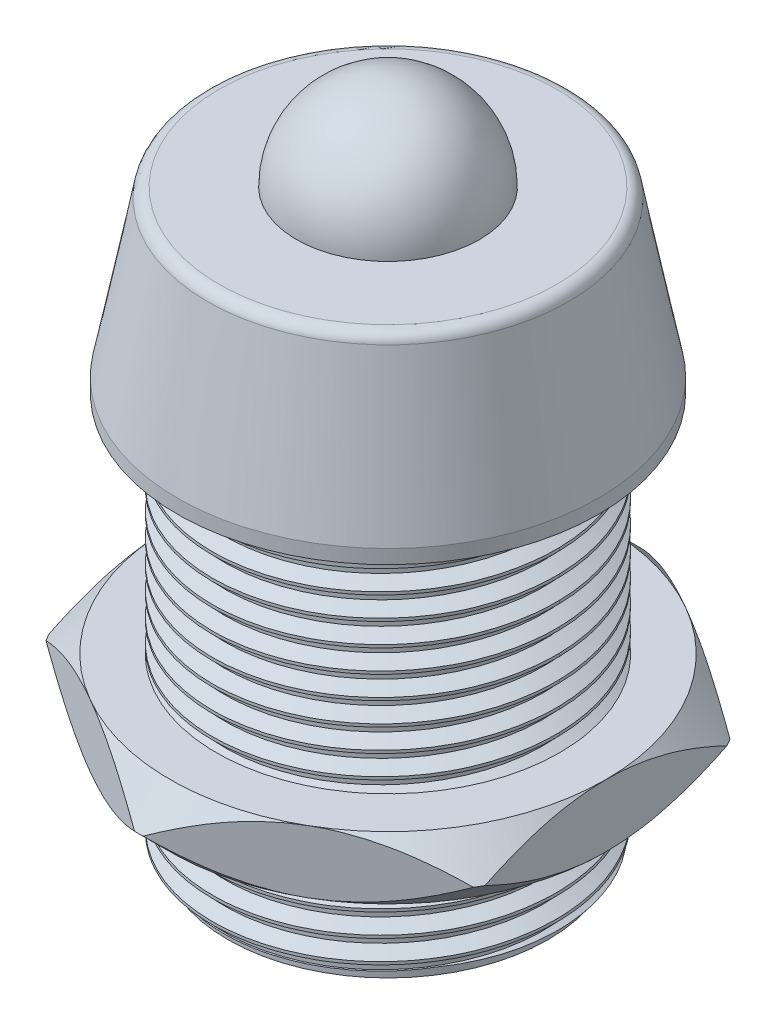
SolidWorks part; units mm, degrees
material "Stainless Steel (ferritic)"
ref_plane "Front Plane" through (0, 0, 0) normal (0, 0, 1) x (1, 0, 0)
ref_plane "Top Plane" through (0, 0, 0) normal (0, 1, 0) x (1, 0, 0)
ref_plane "Right Plane" through (0, 0, 0) normal (1, 0, 0) x (0, 0, -1)
sketch "Sketch1" plane through (0, 0, 0) normal (0, 0, 1) x (1, 0, 0)
  line L0 (0, -1000) -> (0, 49000) construction
  line L2 (0, 5.9) -> (0, -8.6)
  line L3 (0, -8.6) -> (-3.75, -8.6)
  line L4 (-3.75, -8.6) -> (-3.75, -6.3054)
  line L5 (-3.75, -6.3054) -> (-5.5, -6.3054)
  line L6 (-5.5, -6.3054) -> (-5.5, -4.9373)
  line L7 (-5.5, -4.9373) -> (-3.75, -4.9373)
  line L8 (-3.75, -4.9373) -> (-3.75, 0)
  line L9 (55, 0) -> (-55, 0) construction
  line L10 (-3.75, 0) -> (-4.6, 0)
  line L11 (-4.6, 0) -> (-4.6, 3.9)
  line L12 (-4.6, 3.9) -> (-2, 3.9)
  line L13 (-2, 3.9) -> (-2, 5.9)
  line L14 (-2, 5.9) -> (0, 5.9)
  dimension "D1" = 2
  dimension "D2" = 7.5
  dimension "D3" = 8.6
  dimension "D4" = 4
  dimension "D5" = 9.2
  dimension "D6" = 12.5
  dimension "D7" = 11
revolve "Revolve1" add sketch "Sketch1" angle 360 about L0
sketch "Sketch2" plane through (0, -8.6, 0) normal (0, -1, 0) x (1, 0, 0)
  circle A0 centre (0, 0) radius 3.5
  dimension "D1" = 7
extrude "Cut-Extrude1" cut sketch "Sketch2" against normal blind 0.15 flip side to cut
fillet "Fillet1" radius 2 1 edges at (2, 5.9, 0)
chamfer "Chamfer1" distance 0.6985 angle 79 1 edges at (4.6, 3.9, 0) first distance on face at (4.6, 3.9, 0)
thread "Thread1" pitch 0.5 method cut profile "Thread Profile1" start angle 0, offset 0.6, length 8.3, pitch 0.5, diameter 7.5
ref_plane "Plane1" through (3.75, -9.05, 0) normal (0, 0, 1) x (1, 0, 0)
sketch "Thread Profile1" plane through (3.75, -9.05, 0) normal (0, 0, 1) x (1, 0, 0)
  line L0 (0, 0) -> (0, 0.5) construction
  line L11 (0, 0) -> (0, 0.4375)
  line L12 (0, 0.4375) -> (-0.2706, 0.2812)
  line L13 (-0.2706, 0.2812) -> (-0.2706, 0.1562)
  line L15 (-0.2706, 0.1562) -> (0, 0)
  line L17 (-0.2706, 0.2187) -> (0, 0.2187) construction
  point P2 (0, 0)
  dimension "Pitch" = 0.5
  dimension "Profile_Angle" = 60
  dimension "Profile_Land" = 0.125
  dimension "Profile_Height" = 0.2706
sketch "Sketch7" plane through (0, -6.3054, 0) normal (0, -1, 0) x (1, 0, 0)
  line L1 (0, 5.5) -> (-4.7631, 2.75)
  line L2 (-4.7631, 2.75) -> (-4.7631, -2.75)
  line L3 (-4.7631, -2.75) -> (0, -5.5)
  line L4 (0, -5.5) -> (4.7631, -2.75)
  line L5 (4.7631, -2.75) -> (4.7631, 2.75)
  line L6 (4.7631, 2.75) -> (0, 5.5)
  circle A0 centre (0, 0) radius 4.7631 construction
  circle A1 centre (0, 0) radius 5.5 construction
extrude "Cut-Extrude2" cut sketch "Sketch7" against normal up to surface (1.3681 mm away) flip side to cut up to face at (5.5, -4.9373, 0)
fillet "Fillet2" radius 0.254 1 edges at (3.9015, 3.9, 0)
sketch "Sketch8" plane through (0, -4.9373, 0) normal (0, 1, 0) x (1, 0, 0)
  circle A0 centre (0, 0) radius 4.7631
extrude "Cut-Extrude3" cut sketch "Sketch8" against normal blind 5.23 draft 45 flip side to cut
sketch "Sketch9" plane through (0, -6.3054, 0) normal (0, -1, 0) x (1, 0, 0)
  circle A0 centre (0, 0) radius 4.7631
extrude "Cut-Extrude4" cut sketch "Sketch9" against normal blind 3.048 draft 45 flip side to cut
